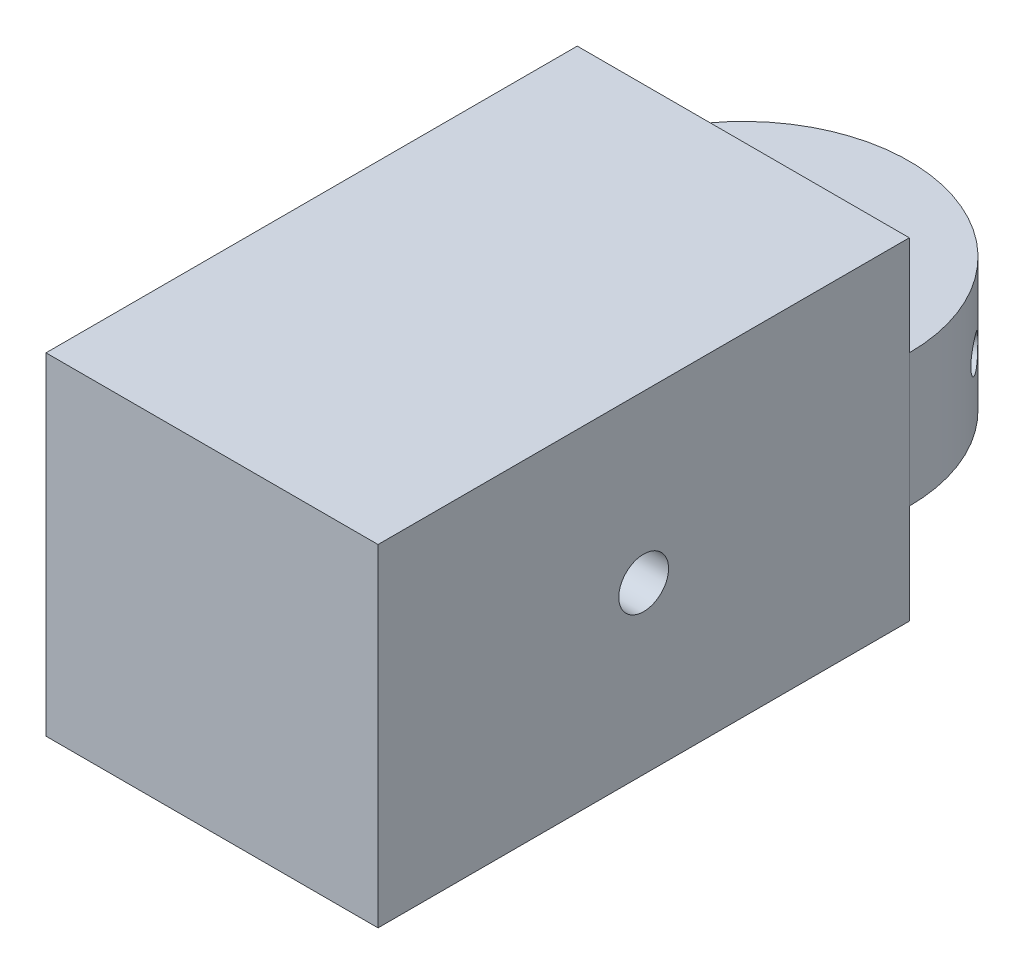
SolidWorks part; units mm, degrees
ref_plane "Front Plane" through (0, 0, 0) normal (0, 0, 1) x (1, 0, 0)
ref_plane "Top Plane" through (0, 0, 0) normal (0, 1, 0) x (1, 0, 0)
ref_plane "Right Plane" through (0, 0, 0) normal (1, 0, 0) x (0, 0, -1)
sketch "Sketch1" plane through (0, 0, 0) normal (0, 0, 1) x (1, 0, 0)
  line L1 (-9.525, 9.525) -> (9.525, 9.525) construction
  line L2 (-9.525, 9.525) -> (-9.525, -9.525) construction
  line L3 (-9.525, -9.525) -> (9.525, -9.525) construction
  line L4 (9.525, 9.525) -> (9.525, -9.525) construction
  line L5 (-9.525, 9.525) -> (9.525, -9.525) construction
  line L6 (-9.525, -9.525) -> (9.525, 9.525) construction
  line L7 (-7.9375, 7.9375) -> (7.9375, 7.9375)
  line L8 (-7.9375, 7.9375) -> (-7.9375, -7.9375)
  line L9 (-7.9375, -7.9375) -> (7.9375, -7.9375)
  line L10 (7.9375, 7.9375) -> (7.9375, -7.9375)
  line L11 (-7.9375, 7.9375) -> (7.9375, -7.9375) construction
  line L12 (-7.9375, -7.9375) -> (7.9375, 7.9375) construction
  point P0 (0, 0)
  point P6 (0, 0)
  dimension "D1" = 19.05
  dimension "D2" = 19.05
  dimension "D3" = 1.5875
extrude "Boss-Extrude1" add sketch "Sketch1" along normal blind 25.4
ref_plane "Plane1" through (0, 0, 0) normal (0, 1, 0) x (1, 0, 0)
sketch "Sketch3" plane through (0, 0, 0) normal (0, 1, 0) x (1, 0, 0)
  line L0 (7.9375, 0) -> (-7.9375, 0) construction
  line L1 (-7.9375, 0) -> (7.9375, 0)
  arc A0 (-7.9375, 0) -> (7.9375, 0) centre (0, 0) cw
extrude "Boss-Extrude3" add sketch "Sketch3" along normal blind 3.175 and the other way blind 3.175
sketch "Sketch4" plane through (7.9375, 0, 0) normal (1, 0, 0) x (0, 0, -1)
  line L0 (-25.4, 0) -> (0, 0) construction
  line L1 (-25.4, -7.9375) -> (-25.4, 7.9375) construction
  line L2 (-12.7, 7.9375) -> (-12.7, -7.9375) construction
  line L3 (-25.4, 7.9375) -> (0, 7.9375) construction
  line L4 (-25.4, -7.9375) -> (0, -7.9375) construction
  line L5 (-25.4, 0) -> (0, 0) construction
  circle A0 centre (-12.7, 0) radius 1.1906
  dimension "D1" = 2.3813
extrude "Cut-Extrude1" cut sketch "Sketch4" against normal through all
sketch "Sketch5" plane through (0, 0, 0) normal (0, 1, 0) x (1, 0, 0)
  line L0 (0, 0) -> (-4.7214, 6.3806)
  line L1 (0, 0) -> (6.3806, 4.7214)
  line L2 (-7.9375, 0) -> (7.9375, 0) construction
  arc A0 (7.9375, 0) -> (-7.9375, 0) centre (0, 0) ccw construction
  point P6 (0, 0)
  point P8 (0, 0)
  point P9 (0, 0)
  point P10 (0, 0)
  point P11 (0, 0)
  dimension "D1" = 53.5
ref_plane "Plane2" through (-4.7214, 0, -6.3806) normal (0.5948, 0, 0.8039) x (0.8039, 0, -0.5948)
sketch "Sketch7" plane through (-4.7214, 0, -6.3806) normal (0.5948, 0, 0.8039) x (0.8039, 0, -0.5948)
  circle A0 centre (0, 0) radius 0.7937
  dimension "D1" = 1.5875
ref_plane "Plane3" through (6.3806, 0, -4.7214) normal (0.8039, 0, -0.5948) x (-0.5948, 0, -0.8039)
sketch "Sketch8" plane through (6.3806, 0, -4.7214) normal (0.8039, 0, -0.5948) x (-0.5948, 0, -0.8039)
  circle A0 centre (0, 0) radius 0.7937
  dimension "D1" = 1.5875
extrude "Cut-Extrude3" cut sketch "Sketch8" against normal up to vertex (7.9375 mm away) contours A0 up to point (0, 0, 0)
extrude "Cut-Extrude4" cut sketch "Sketch7" along normal up to vertex (7.9375 mm away) contours A0 up to point (0, 0, 0)
